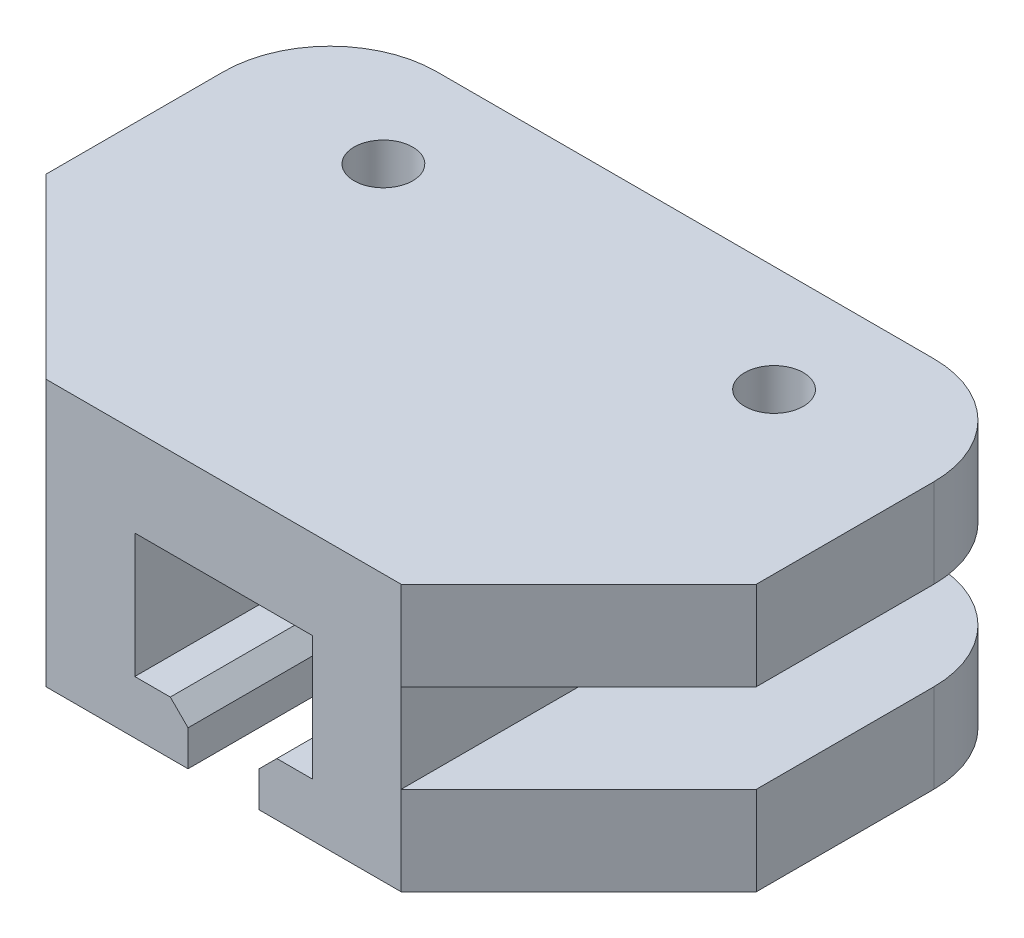
SolidWorks part; units mm, degrees
ref_plane "前视基准面" through (0, 0, 0) normal (0, 0, 1) x (1, 0, 0)
ref_plane "上视基准面" through (0, 0, 0) normal (0, 1, 0) x (1, 0, 0)
ref_plane "右视基准面" through (0, 0, 0) normal (1, 0, 0) x (0, 0, -1)
sketch "草图1" plane through (0, 0, 0) normal (0, 0, 1) x (1, 0, 0)
  line L1 (0, 0) -> (-20, 0)
  line L2 (0, 0) -> (0, 20)
  line L3 (0, 20) -> (-20, 20)
  line L4 (-20, 0) -> (-20, 20)
  dimension "D1" = 20
  dimension "D2" = 20
extrude "拉伸-薄壁1" add sketch "草图1" along normal blind 30 thin thin type one direction reverse wall 5
sketch "草图2" plane through (0, 0, 0) normal (1, 0, 0) x (0, 0, -1)
  line L0 (0, 0) -> (0, 20) construction
  line L1 (0, 10) -> (-20, 10)
  line L2 (0, 10) -> (0, 30)
  line L3 (0, 30) -> (-20, 30)
  line L4 (-20, 10) -> (-20, 30)
  line L5 (-30, 20) -> (0, 20) construction
  dimension "D1" = 20
  dimension "D2" = 10
  dimension "D3" = 20
extrude "凸台-拉伸1" add sketch "草图2" along normal blind 20 and the other way blind 40
sketch "草图4" [suppressed] plane through (0, 20, 0) normal (0, 1, 0) x (1, 0, 0)
  line L1 (-20, 0) -> (0, 0)
  line L2 (-20, 0) -> (-20, -20)
  line L3 (-20, -20) -> (0, -20)
  line L4 (0, 0) -> (0, -20)
extrude "凸台-拉伸2" [suppressed] add sketch "草图4" along normal blind 15
sketch "草图5" plane through (0, 0, 20) normal (0, 0, 1) x (1, 0, 0)
  line L0 (-40, 30) -> (-40, 10) construction
  line L1 (-20, 20) -> (-40, 20)
  line L2 (-20, 20) -> (-20, 30)
  line L3 (-20, 30) -> (-40, 30)
  line L4 (-40, 20) -> (-40, 30)
  line L5 (20, 30) -> (20, 10) construction
  line L6 (0, 20) -> (20, 20)
  line L7 (0, 20) -> (0, 30)
  line L8 (0, 30) -> (20, 30)
  line L9 (20, 20) -> (20, 30)
  dimension "D1" = 20
  dimension "D2" = 10
extrude "切除-拉伸1" cut sketch "草图5" against normal blind 35
sketch "草图6" plane through (0, 30, 0) normal (0, 1, 0) x (1, 0, 0)
  line L0 (20, 0) -> (20, -20) construction
  line L1 (-40, 0) -> (-40, -20) construction
  line L2 (-20, 0) -> (0, 0) construction
  circle A0 centre (-21, -10) radius 1.5
  circle A1 centre (1, -10) radius 1.5
  dimension "D1" = 3
  dimension "D2" = 3
  dimension "D3" = 19
  dimension "D4" = 19
  dimension "D5" = 10
  dimension "D6" = 10
extrude "切除-拉伸2" cut sketch "草图6" against normal blind 35
sketch "草图7" plane through (0, 0, 30) normal (0, 0, 1) x (1, 0, 0)
  line L1 (-15, 15) -> (-5, 15)
  line L2 (-15, 15) -> (-15, 5)
  line L3 (-15, 5) -> (-5, 5)
  line L4 (-5, 15) -> (-5, 5)
extrude "切除-拉伸3" cut sketch "草图7" against normal blind 35
sketch "草图8" plane through (0, 20, 0) normal (0, 1, 0) x (1, 0, 0)
  line L1 (-20, 0) -> (0, 0)
  line L2 (-20, 0) -> (-20, -20)
  line L3 (-20, -20) -> (0, -20)
  line L4 (0, 0) -> (0, -20)
extrude "切除-拉伸4" cut sketch "草图8" along normal blind 23
sketch "草图9" plane through (0, 20, 0) normal (0, 1, 0) x (1, 0, 0)
  line L0 (-40, 0) -> (20, 0) construction
  line L1 (-15, 0) -> (-5, 0)
  line L2 (-15, 0) -> (-15, -30)
  line L3 (-15, -30) -> (-5, -30)
  line L4 (-5, 0) -> (-5, -30)
  line L5 (0, -30) -> (-20, -30) construction
  line L6 (0, -30) -> (0, -20) construction
  dimension "D1" = 10
  dimension "D2" = 5
extrude "凸台-拉伸3" [suppressed] add sketch "草图9" along normal blind 5
sketch "草图10" plane through (0, 10, 0) normal (0, -1, 0) x (1, 0, 0)
  line L1 (-40, 20) -> (-20, 20)
  line L2 (-40, 20) -> (-40, 0)
  line L3 (-40, 0) -> (-20, 0)
  line L4 (-20, 20) -> (-20, 0)
  line L5 (0, 20) -> (20, 20)
  line L6 (0, 20) -> (0, 0)
  line L7 (0, 0) -> (20, 0)
  line L8 (20, 20) -> (20, 0)
extrude "切除-拉伸5" cut sketch "草图10" against normal blind 5
sketch "草图11" [suppressed] plane through (0, 15, 0) normal (0, -1, 0) x (1, 0, 0)
  line L0 (-20, 0) -> (0, 0) construction
  line L1 (-20, 20) -> (-15.3668, 20)
  line L2 (-20, 20) -> (-20, 0)
  line L3 (-20, 0) -> (-15.3668, 0)
  line L4 (-15.3668, 20) -> (-15.3668, 0)
  line L6 (0, 20) -> (-4.4381, 20)
  line L7 (0, 20) -> (0, 0)
  line L8 (0, 0) -> (-4.4381, 0)
  line L9 (-4.4381, 20) -> (-4.4381, 0)
chamfer "倒角1" distance 10 angle 45 2 edges at (0, 17.5, 20) (-20, 17.5, 20)
sketch "草图12" plane through (0, 15, 0) normal (0, -1, 0) x (1, 0, 0)
  line L0 (-20, 11.118) -> (-20, 30) construction
  line L1 (-20, 15) -> (0, 15)
  line L2 (-20, 15) -> (-20, 0)
  line L3 (-20, 0) -> (0, 0)
  line L4 (0, 15) -> (0, 0)
  dimension "D1" = 15
extrude "切除-拉伸6" cut sketch "草图12" along normal blind 5
sketch "草图13" plane through (0, 15, 0) normal (0, -1, 0) x (1, 0, 0)
  line L0 (20, 0) -> (-40, 0) construction
  line L1 (-40, 20) -> (-30, 20)
  line L2 (-40, 20) -> (-40, 0)
  line L3 (-40, 0) -> (-30, 0)
  line L4 (-30, 20) -> (-30, 0)
  line L6 (10, 20) -> (20, 20)
  line L7 (10, 20) -> (10, 0)
  line L8 (10, 0) -> (20, 0)
  line L9 (20, 20) -> (20, 0)
  dimension "D1" = 10
  dimension "D2" = 10
extrude "切除-拉伸7" cut sketch "草图13" against normal blind 5
sketch "草图14" plane through (0, 0, 0) normal (0, -1, 0) x (1, 0, 0)
  line L1 (-30, 20) -> (10, 20)
  line L2 (-30, 20) -> (-30, 0)
  line L3 (-30, 0) -> (10, 0)
  line L4 (10, 20) -> (10, 0)
extrude "凸台-拉伸4" add sketch "草图14" against normal blind 10
sketch "草图15" plane through (0, 0, 30) normal (0, 0, 1) x (1, 0, 0)
  line L0 (-5, 5) -> (-5, 15) construction
  line L1 (-15, 5) -> (-5, 5)
  line L2 (-15, 5) -> (-15, 10)
  line L3 (-15, 10) -> (-5, 10)
  line L4 (-5, 5) -> (-5, 10)
extrude "切除-拉伸8" cut sketch "草图15" against normal blind 37
chamfer "倒角2" distance 10 angle 45 2 edges at (0, 5, 20) (-20, 5, 20)
sketch "草图16" plane through (0, 10, 0) normal (0, 1, 0) x (1, 0, 0)
  circle A0 centre (-21, -10) radius 1.65
  circle A1 centre (1, -10) radius 1.65
  dimension "D1" = 3.3
  dimension "D2" = 3.3
extrude "切除-拉伸9" cut sketch "草图16" against normal blind 10 and the other way blind 37
sketch "草图18" plane through (0, 20, 0) normal (0, 1, 0) x (1, 0, 0)
  line L0 (10, -20) -> (10, 0) construction
  line L1 (-30, 0) -> (10, 0)
  line L2 (-30, 0) -> (-30, -4)
  line L3 (-30, -4) -> (10, -4)
  line L4 (10, 0) -> (10, -4)
  dimension "D1" = 4
extrude "切除-拉伸10" cut sketch "草图18" against normal blind 35
sketch "草图19" plane through (0, 0, 0) normal (0, -1, 0) x (1, 0, 0)
  line L0 (-30, 4) -> (10, 4) construction
  line L1 (-15, 24) -> (-5, 24)
  line L2 (-15, 24) -> (-15, 16)
  line L3 (-15, 16) -> (-5, 16)
  line L4 (-5, 24) -> (-5, 16)
  line L5 (10, 4) -> (10, 20) construction
  line L6 (-30, 20) -> (-30, 4) construction
  dimension "D1" = 10
  dimension "D2" = 12
  dimension "D3" = 15
  dimension "D4" = 15
  dimension "D5" = 8
extrude "凸台-拉伸5" add sketch "草图19" along normal blind 10
sketch "草图20" plane through (-15, 0, 0) normal (-1, 0, 0) x (0, 0, 1)
  line L0 (24, -10) -> (24, 0) construction
  line L1 (24, 0) -> (16, 0) construction
  circle A0 centre (20, -3) radius 1.5
  dimension "D1" = 3
  dimension "D2" = 4
  dimension "D3" = 3
extrude "切除-拉伸11" cut sketch "草图20" against normal blind 30
fillet "圆角1" radius 6 4 edges at (10, 17.5, 4) (10, 5, 4) (-30, 5, 4) (-30, 17.5, 4)
sketch "草图21" plane through (0, 0, 0) normal (0, -1, 0) x (1, 0, 0)
  line L1 (-15, 16) -> (-5, 16)
  line L2 (-15, 16) -> (-15, 4)
  line L3 (-15, 4) -> (-5, 4)
  line L4 (-5, 16) -> (-5, 4)
extrude "切除-拉伸12" cut sketch "草图21" against normal blind 1
sketch "草图23" plane through (0, 0, 0) normal (0, -1, 0) x (1, 0, 0)
  line L1 (-41.0004, 36.2493) -> (19.4857, 36.2493)
  line L2 (-41.0004, 36.2493) -> (-41.0004, -2.6274)
  line L3 (-41.0004, -2.6274) -> (19.4857, -2.6274)
  line L4 (19.4857, 36.2493) -> (19.4857, -2.6274)
extrude "切除-拉伸13" cut sketch "草图23" against normal blind 5 and the other way blind 18
sketch "草图24" plane through (0, 0, 30) normal (0, 0, 1) x (1, 0, 0)
  line L1 (-15, 5) -> (-12, 5)
  line L2 (-15, 5) -> (-15, 8)
  line L3 (-15, 8) -> (-12, 8)
  line L4 (-12, 5) -> (-12, 8)
  line L5 (-5, 5) -> (-8, 5)
  line L6 (-5, 5) -> (-5, 8)
  line L7 (-5, 8) -> (-8, 8)
  line L8 (-8, 5) -> (-8, 8)
  dimension "D1" = 3
  dimension "D2" = 3
  dimension "D3" = 3
  dimension "D4" = 3
extrude "凸台-拉伸6" add sketch "草图24" against normal blind 25
chamfer "倒角3" distance 3 angle 45 2 edges at (-5, 6.5, 5) (-15, 6.5, 5)
chamfer "倒角4" distance 1 angle 45 2 edges at (-12, 8, 17.5) (-8, 8, 17.5)
chamfer "倒角5" distance 3 angle 45 2 edges at (-20, 12.5, 15) (0, 12.5, 15)
